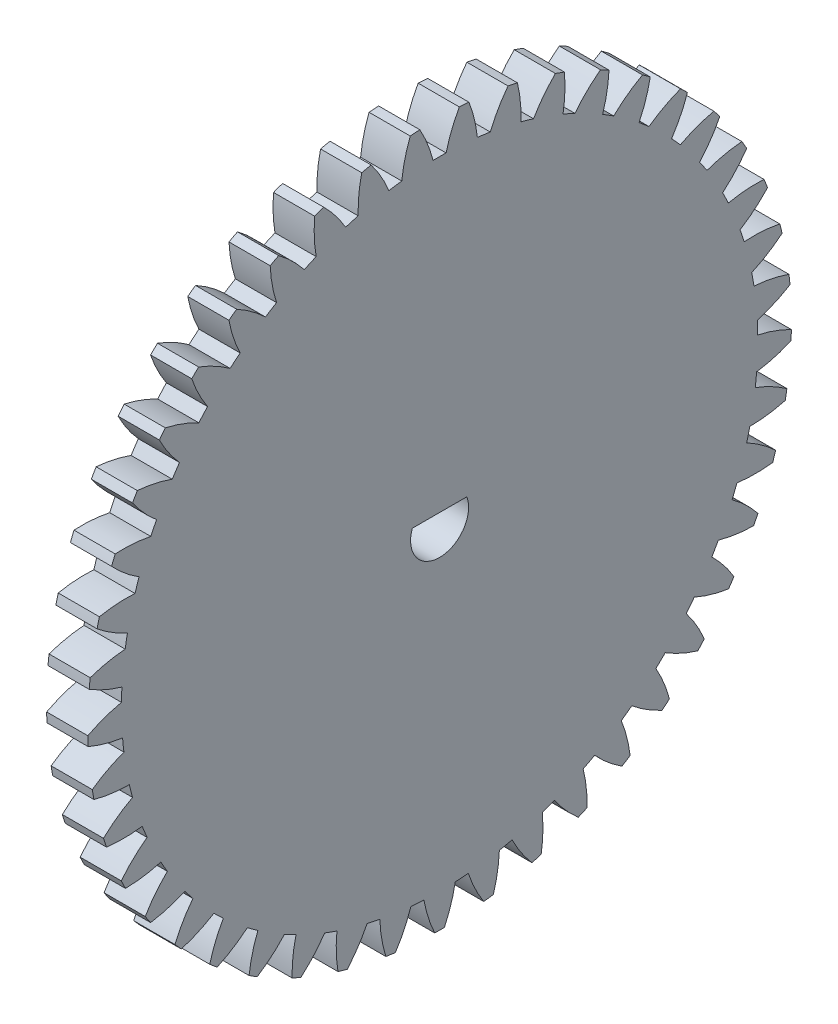
SolidWorks part; units mm, degrees
ref_plane "Plane1" through (0, 0, 0) normal (0, 0, 1) x (1, 0, 0)
ref_plane "Plane2" through (0, 0, 0) normal (0, 1, 0) x (1, 0, 0)
ref_plane "Plane3" through (0, 0, 0) normal (1, 0, 0) x (0, 0, -1)
sketch "HoldingSke" plane through (0, 0, 0) normal (0, 1, 0) x (1, 0, 0)
  line L0 (0, 0) -> (0.3536, -0.3536)
  line L1 (-15, 0) -> (100, 0) construction
  line L2 (0, 0) -> (-2.1039, 2.3779)
  line L3 (0, 0) -> (-11.863, 4.5341)
  line L4 (0, 0) -> (6.1066, 6.1066)
  line L5 (0, 0) -> (-46.8476, -17.4728)
  line L6 (0, 0) -> (-4.5593, -3.0762)
  line L7 (-2.1039, 2.3779) -> (8.6586, 51.2059)
  line L8 (-76.2, 54.61) -> (-76.1, 54.61)
  line L9 (-71.009, 38.7566) -> (-53.1078, 45.2721)
  line L10 (-76.2, 71.12) -> (104.1128, 71.12)
  line L11 (0, 0) -> (-5.5, 0)
  line L12 (-76.2, 101.6) -> (-76.133, 101.6)
  line L13 (24.9733, 27.94) -> (52.9518, 28.4284)
  line L14 (24.9733, 27.94) -> (24.9743, 27.94)
  line L15 (24.9733, 27.94) -> (100.4006, 29.5858)
  line L16 (-63.627, -2) -> (-12.827, -2)
  circle A0 centre (0, 0) radius 0.4
  circle A1 centre (0, 0) radius 37.5
  circle A2 centre (0, 0) radius 37.5
  circle A3 centre (0, 0) radius 0.4
  dimension "MHD" = 75
  dimension "Hub_dia" = 75
  dimension "Bore" = 0.8
  dimension "MBD" = 0.8
  dimension "Num_teeth" = 45
  dimension "Pitch" = 0.5
  dimension "Overall_len" = 50
  dimension "Show_teeth" = 45
  dimension "Thickness" = 5.5
  dimension "OAL" = 50.0001
  dimension "T_dim" = 0.1
  dimension "Ap" = 20
  dimension "H" = 19.05
  dimension "Pitch_radius" = 180.3128
  dimension "Width" = 5.5
  dimension "Backlash" = 0.067
  dimension "Addendum_fac" = 1
  dimension "Dedendum_fac" = 1.25
  dimension "Clearance_fac" = 0.25
  dimension "Dedendum_add" = 0.001
  dimension "Module" = 2
sketch "BasProSke" plane through (0, 0, 0) normal (0, 1, 0) x (1, 0, 0)
  line L0 (-10, 0) -> (60, 0) construction
  line L1 (0, 0) -> (0, 47)
  line L2 (0, 0) -> (5.5, 0)
  line L3 (5.5, 0) -> (5.5, 47)
  line L4 (5.5, 47) -> (0, 47)
  dimension "Thickness" = 5.5
  dimension "Diameter" = 94
revolve "Base-Revolve" add sketch "BasProSke" angle 360 about L0
sketch "TooCutSke" plane through (0, 0, 0) normal (1, 0, 0) x (0, 0, -1)
  line L1 (0, 0) -> (0, 107) construction
  line L2 (0, 0) -> (-1.6877, 44.9683) construction
  line L3 (0, 0) -> (-6.2748, 89.7339) construction
  line L4 (-1.6877, 44.9683) -> (-3.1374, 44.867) construction
  arc A0 (0.8706, 42.4901) -> (-0.8706, 42.4901) centre (0, 0) ccw
  arc A1 (2.6509, 46.9506) -> (-2.6509, 46.9506) centre (0, 0) ccw
  circle A2 centre (0, 0) radius 45 construction
  circle A3 centre (0, 0) radius 42.2862 construction
  arc A4 (-0.8706, 42.4901) -> (-2.6509, 46.9506) centre (-18.3289, 38.1074) ccw
  arc A5 (2.6509, 46.9506) -> (0.8706, 42.4901) centre (18.3289, 38.1074) ccw
  dimension "Root_dia" = 84.998
  dimension "Overcut_dia" = 94.0508
  dimension "Pitch_dia" = 90
  dimension "Base_dia" = 84.5723
  dimension "Flank_rad" = 18
  dimension "Half_ang" = 4
  dimension "Half_CT" = 1.4532
extrude "ToothCut" cut sketch "TooCutSke" along normal through all
fillet "Breaks" [suppressed] radius 0.04 tangent propagation no
fillet "RootFillets" [suppressed] radius 0.501
pattern_circular "TeethCuts" count 45 every 8 about axis through (-10, 0, 0) along (1, 0, 0) of "ToothCut", "RootFillets", "Breaks"
sketch "HubNeaOneSke" plane through (0, 0, 0) normal (-1, 0, 0) x (0, 0, 1)
  circle A0 centre (0, 0) radius 37.5
  dimension "Diameter" = 75
extrude "HubNearOne" [suppressed] add sketch "HubNeaOneSke" along normal blind 44.5001
sketch "HubNeaBotSke" plane through (0, 0, 0) normal (-1, 0, 0) x (0, 0, 1)
  circle A0 centre (0, 0) radius 37.5
  dimension "Diameter" = 75
extrude "HubNearBoth" [suppressed] add sketch "HubNeaBotSke" along normal blind 22.25
ref_plane "FarPln" through (5.5, 0, 0) normal (1, 0, 0) x (0, 0, -1)
sketch "HubFarSke" plane through (5.5, 0, 0) normal (1, 0, 0) x (0, 0, -1)
  circle A0 centre (0, 0) radius 37.5
  dimension "Diameter" = 75
extrude "HubFar" [suppressed] add sketch "HubFarSke" along normal blind 22.25
sketch "BorSke" plane through (0, 0, 0) normal (1, 0, 0) x (0, 0, -1)
  circle A0 centre (0, 0) radius 0.4
  dimension "Diameter" = 0.8
extrude "Bore" cut sketch "BorSke" along normal mid plane 100.0001
sketch "KeySke" plane through (0, 0, 0) normal (1, 0, 0) x (0, 0, -1)
  line L0 (-0.05, 0) -> (-0.05, 0.5)
  line L1 (-0.05, 0.5) -> (0.05, 0.5)
  line L2 (0.05, 0.5) -> (0.05, 0)
  line L3 (0, 0) -> (0, 34) construction
  line L4 (-0.05, 0) -> (0.05, 0)
  dimension "Offset" = 0.5
  dimension "Width" = 0.1
extrude "Keyway" [suppressed] cut sketch "KeySke" along normal mid plane 100.0001
pattern_circular "Keyway2" [suppressed] count 2 every 90 about axis through (-10, 0, 0) along (1, 0, 0)
sketch "Croquis1" plane through (5.5, 0, 0) normal (1, 0, 0) x (0, 0, -1)
  line L0 (0, -3.875) -> (0, 1.325) construction
  line L1 (0, 1.325) -> (3.6414, 1.325)
  line L2 (0, 1.325) -> (-3.6414, 1.325)
  arc A2 (-3.6414, 1.325) -> (3.6414, 1.325) centre (0, 0) ccw
  dimension "D1" = 7.75
  dimension "D2" = 5.2
extrude "Cortar-Extruir1" cut sketch "Croquis1" against normal blind 6
equation "' \"Module@HoldingSke\" = 6.35"
equation "' \"Num_teeth@HoldingSke\" = 12"
equation "' \"Ap@HoldingSke\" =  20"
equation "' \"Ap@HoldingSke\" = 20"
equation "' \"Width@HoldingSke\" = 0.5 * 25.4"
equation "' \"Hub_dia@HoldingSke\"= 1 * 25.4"
equation "' \"Hub_dia@HoldingSke\" = 1 * 25.4"
equation "' \"Overall_len@HoldingSke\" = 1.0 * 25.4"
equation "' \"Bore@HoldingSke\" = 0.75 * 25.4"
equation "' \"T_dim@HoldingSke\" = 0.1 * 25.4"
equation "' \"Width@KeySke\" = 0.25 * 25.4"
equation "' \"Show_teeth@HoldingSke\" = 13"
equation "' \"Backlash@HoldingSke\" = 0.009 * 25.4"
equation "' \"Addendum_fac@HoldingSke\" = 1.0"
equation "' \"Dedendum_fac@HoldingSke\" = 1.25"
equation "' \"Dedendum_add@HoldingSke\" = 0.00005 * 25.4"
equation "' \"Clearance_fac@HoldingSke\" = 0.25"
equation "\"Pitch@HoldingSke\" = 1 / \"Module@HoldingSke\""
equation "\"Overcut_dia@TooCutSke\" = (\"Num_teeth@HoldingSke\" + 2 * \"Addendum_fac@HoldingSke\") / \"Pitch@HoldingSke\" + 0.002 * 25.4"
equation "\"Pitch_dia@TooCutSke\" = \"Num_teeth@HoldingSke\" / \"Pitch@HoldingSke\""
equation "\"Base_dia@TooCutSke\" = \"Num_teeth@HoldingSke\" / \"Pitch@HoldingSke\" * cos((\"Ap@HoldingSke\"  * 3.14159265 / 180))"
equation "\"Root_dia@TooCutSke\" = (\"Num_teeth@HoldingSke\" + 2) / \"Pitch@HoldingSke\" - 2 * (\"Addendum_fac@HoldingSke\" + \"Dedendum_fac@HoldingSke\") / \"Pitch@HoldingSke\" - \"Dedendum_add@HoldingSke\" * 2"
equation "\"Half_ang@TooCutSke\" = 180 / \"Num_teeth@HoldingSke\""
equation "\"Half_CT@TooCutSke\" = \"Num_teeth@HoldingSke\" / \"Pitch@HoldingSke\" * sin((3.14159265 / 2 / \"Num_teeth@HoldingSke\")) / 2 - 7 * \"Backlash@HoldingSke\" / 4"
equation "\"Flank_rad@TooCutSke\" = \"Num_teeth@HoldingSke\" / \"Pitch@HoldingSke\" / 5"
equation "\"Radius@RootFillets\" = \"Clearance_fac@HoldingSke\" / \"Pitch@HoldingSke\" + \"Dedendum_add@HoldingSke\""
equation "\"Break_rad@Breaks\" = 0.02 / \"Pitch@HoldingSke\""
equation "\"Thickness@HoldingSke\" = \"Width@HoldingSke\""
equation "\"OAL@HoldingSke\" = \"Thickness@HoldingSke\""
equation "\"MHD@HoldingSke\" = (\"Num_teeth@HoldingSke\" + 2) / \"Pitch@HoldingSke\" - 2 * (\"Addendum_fac@HoldingSke\" + \"Dedendum_fac@HoldingSke\")  / \"Pitch@HoldingSke\" - \"Dedendum_add@HoldingSke\" * 2"
equation "\"MBD@HoldingSke\" = (\"Num_teeth@HoldingSke\" + 2) / \"Pitch@HoldingSke\" - 2 * (\"Addendum_fac@HoldingSke\" + \"Dedendum_fac@HoldingSke\")  / \"Pitch@HoldingSke\" - \"Dedendum_add@HoldingSke\" * 2 - 0.002 * 25.4"
equation "\"MHD@HoldingSke\" = ((sgn( \"MHD@HoldingSke\" - \"Hub_dia@HoldingSke\" )-1)*( \"MHD@HoldingSke\" - \"Hub_dia@HoldingSke\" ))/-2+ \"Hub_dia@HoldingSke\""
equation "\"MBD@HoldingSke\" = ((sgn( \"MBD@HoldingSke\" - \"Bore@HoldingSke\" )-1)*( \"MBD@HoldingSke\" - \"Bore@HoldingSke\" ))/-2+ \"Bore@HoldingSke\""
equation "\"OAL@HoldingSke\" = ((sgn( \"OAL@HoldingSke\" - \"Overall_len@HoldingSke\" )+1)*( \"OAL@HoldingSke\" - \"Overall_len@HoldingSke\" ))/2 + \"Overall_len@HoldingSke\" + 0.000002 * 25.4"
equation "\"Num_teeth@TeethCuts\" = int( \"Show_teeth@HoldingSke\" ) + 1"
equation "\"Num_teeth@TeethCuts\" = ((sgn( \"Num_teeth@TeethCuts\" - \"Num_teeth@HoldingSke\" )-1)*( \"Num_teeth@TeethCuts\" - \"Num_teeth@HoldingSke\" ))/-2+ \"Num_teeth@HoldingSke\""
equation "\"Num_teeth@TeethCuts\" = ((sgn( \"Num_teeth@TeethCuts\" - 2.0)+1)*( \"Num_teeth@TeethCuts\" - 2.0))/2 +2.0"
equation "\"Angle@TeethCuts\" = 360.0 / \"Num_teeth@HoldingSke\""
equation "\"Diameter@BasProSke\" = (\"Num_teeth@HoldingSke\" + 2 * \"Addendum_fac@HoldingSke\") / \"Pitch@HoldingSke\""
equation "\"Thickness@BasProSke\"  = \"Thickness@HoldingSke\""
equation "' \"Fillet_rad@BasProSke\" =  \"Thickness@HoldingSke\" * 0.05"
equation "' \"Fillet_rad@BasProSke\" = \"Thickness@HoldingSke\" * 0.05"
equation "\"MHD@HoldingSke\" = ((sgn( \"MHD@HoldingSke\" - \"Root_dia@TooCutSke\" )-1)*( \"MHD@HoldingSke\" - \"Root_dia@TooCutSke\" ))/-2+ \"Root_dia@TooCutSke\""
equation "\"Diameter@HubNeaOneSke\" = \"MHD@HoldingSke\""
equation "\"Length@HubNearOne\" = \"OAL@HoldingSke\" - \"Thickness@BasProSke\""
equation "\"Diameter@HubNeaBotSke\" = \"MHD@HoldingSke\""
equation "\"Length@HubNearBoth\" = ( \"OAL@HoldingSke\" - \"Thickness@BasProSke\" ) / 2.0"
equation "\"Thickness@FarPln\" = \"Thickness@BasProSke\""
equation "\"Diameter@HubFarSke\" = \"MHD@HoldingSke\""
equation "\"Length@HubFar\" = ( \"OAL@HoldingSke\" - \"Thickness@BasProSke\" ) / 2.0"
equation "\"Diameter@BorSke\" = \"MBD@HoldingSke\""
equation "\"D1@Bore\" = \"OAL@HoldingSke\" * 2.0"
equation "\"D1@Keyway\" = \"OAL@HoldingSke\" * 2.0"
equation "\"Offset@KeySke\" = \"T_dim@HoldingSke\" + \"MBD@HoldingSke\" / 2.0"
